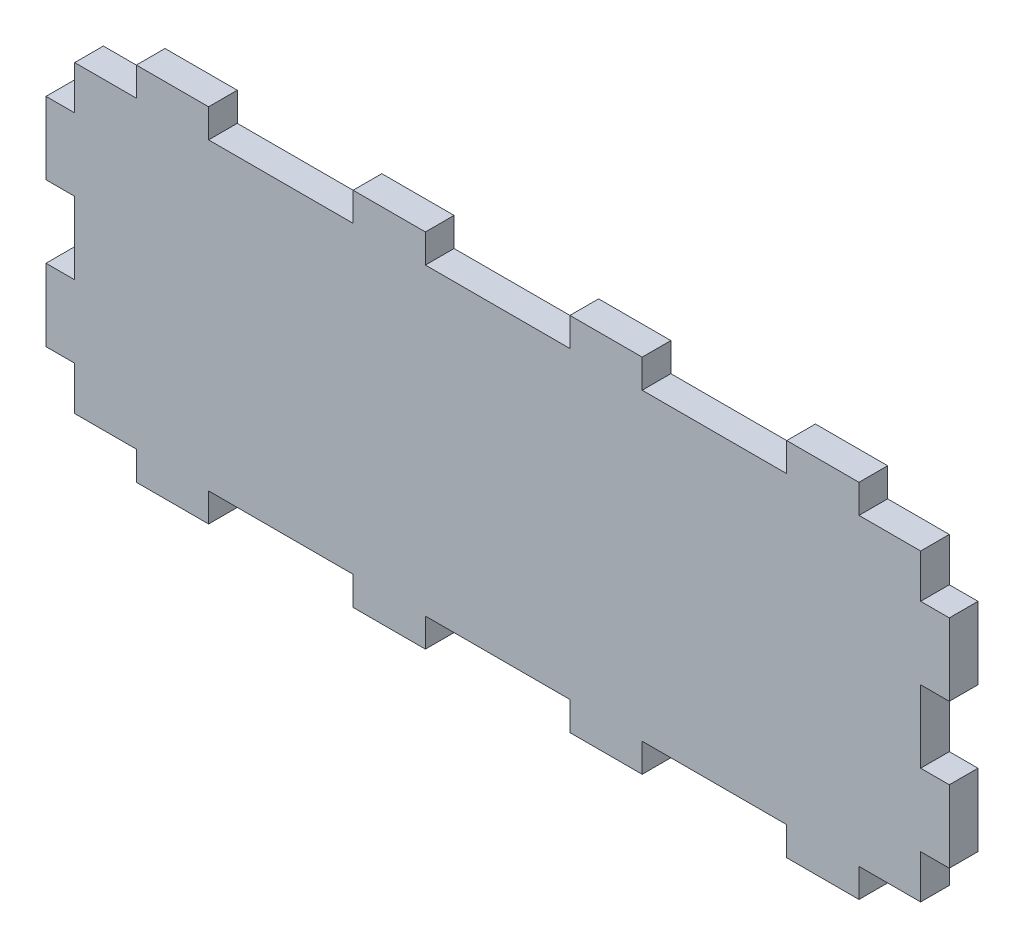
SolidWorks part; units mm, degrees
ref_plane "Front Plane" through (0, 0, 0) normal (0, 0, 1) x (1, 0, 0)
ref_plane "Top Plane" through (0, 0, 0) normal (0, 1, 0) x (1, 0, 0)
ref_plane "Right Plane" through (0, 0, 0) normal (1, 0, 0) x (0, 0, -1)
sketch "Sketch1" plane through (0, 0, 0) normal (0, 0, 1) x (1, 0, 0)
  line L1 (0, 0) -> (100, 0)
  line L2 (0, 0) -> (0, -40)
  line L3 (0, -40) -> (100, -40)
  line L4 (100, 0) -> (100, -40)
  dimension "D1" = 40
  dimension "D2" = 100
extrude "Boss-Extrude1" add sketch "Sketch1" along normal blind 3.175
sketch "Sketch2" plane through (0, 0, 3.175) normal (0, 0, 1) x (1, 0, 0)
  line L0 (0, -20) -> (100, -20) construction
  line L1 (0, 0) -> (0, -40) construction
  line L2 (100, -40) -> (100, 0) construction
  line L3 (50, 0) -> (50, -40) construction
  line L4 (100, 0) -> (0, 0) construction
  line L5 (0, -40) -> (100, -40) construction
  line L6 (10, -40) -> (10, -36.825)
  line L7 (10, -3.175) -> (0, -3.175)
  line L11 (42, -40) -> (58, -40)
  line L13 (42, -36.825) -> (58, -36.825)
  line L14 (58, -40) -> (58, -36.825)
  line L15 (66, -40) -> (82, -40)
  line L16 (66, -40) -> (66, -36.825)
  line L17 (66, -36.825) -> (82, -36.825)
  line L18 (82, -40) -> (82, -36.825)
  line L19 (100, -40) -> (90, -40)
  line L20 (100, -40) -> (100, -36.825)
  line L21 (100, -36.825) -> (90, -36.825)
  line L22 (90, -40) -> (90, -36.825)
  line L23 (0, -36.825) -> (10, -36.825)
  line L24 (0, -40) -> (0, -36.825)
  line L25 (0, -40) -> (10, -40)
  line L26 (18, -40) -> (18, -36.825)
  line L27 (34, -36.825) -> (18, -36.825)
  line L28 (34, -40) -> (34, -36.825)
  line L29 (34, -40) -> (18, -40)
  line L30 (42, -40) -> (42, -36.825)
  line L31 (34, 0) -> (18, 0)
  line L32 (0, 0) -> (10, 0)
  line L33 (100, -3.175) -> (90, -3.175)
  line L34 (42, 0) -> (42, -3.175)
  line L35 (34, 0) -> (34, -3.175)
  line L36 (34, -3.175) -> (18, -3.175)
  line L37 (18, 0) -> (18, -3.175)
  line L38 (0, 0) -> (0, -3.175)
  line L40 (90, 0) -> (90, -3.175)
  line L41 (100, 0) -> (100, -3.175)
  line L42 (100, 0) -> (90, 0)
  line L43 (82, 0) -> (82, -3.175)
  line L44 (66, -3.175) -> (82, -3.175)
  line L45 (66, 0) -> (66, -3.175)
  line L46 (66, 0) -> (82, 0)
  line L47 (58, 0) -> (58, -3.175)
  line L48 (42, -3.175) -> (58, -3.175)
  line L50 (42, 0) -> (58, 0)
  line L51 (10, 0) -> (10, -3.175)
  dimension "D4" = 3.175
  dimension "D5" = 16
  dimension "D6" = 3.175
  dimension "D7" = 8
  dimension "D8" = 3.175
  dimension "D9" = 8
extrude "Cut-Extrude1" cut sketch "Sketch2" against normal up to next
sketch "Sketch3" plane through (0, 0, 3.175) normal (0, 0, 1) x (1, 0, 0)
  line L0 (0, -20) -> (100, -20) construction
  line L1 (0, -3.175) -> (0, -36.825) construction
  line L2 (100, -36.825) -> (100, -3.175) construction
  line L3 (50, -3.175) -> (50, -36.825) construction
  line L4 (42, -3.175) -> (58, -3.175) construction
  line L5 (58, -36.825) -> (42, -36.825) construction
  line L6 (3.175, -36.825) -> (3.175, -32)
  line L7 (0, -32) -> (3.175, -32)
  line L8 (0, -24) -> (0, -16)
  line L9 (0, -16) -> (3.175, -16)
  line L10 (3.175, -24) -> (3.175, -16)
  line L11 (0, -3.175) -> (3.175, -3.175)
  line L12 (0, -3.175) -> (0, -8)
  line L13 (0, -8) -> (3.175, -8)
  line L14 (3.175, -3.175) -> (3.175, -8)
  line L15 (0, -36.825) -> (0, -32)
  line L16 (0, -36.825) -> (3.175, -36.825)
  line L17 (0, -24) -> (3.175, -24)
  line L18 (100, -24) -> (96.825, -24)
  line L19 (100, -36.825) -> (96.825, -36.825)
  line L20 (100, -36.825) -> (100, -32)
  line L21 (96.825, -3.175) -> (96.825, -8)
  line L22 (100, -8) -> (96.825, -8)
  line L23 (100, -3.175) -> (100, -8)
  line L24 (100, -3.175) -> (96.825, -3.175)
  line L25 (96.825, -24) -> (96.825, -16)
  line L26 (100, -16) -> (96.825, -16)
  line L27 (100, -24) -> (100, -16)
  line L28 (100, -32) -> (96.825, -32)
  line L29 (96.825, -36.825) -> (96.825, -32)
  point P24 (3.175, -20)
  point P37 (96.825, -20)
  dimension "D1" = 3.175
  dimension "D2" = 3.175
  dimension "D3" = 4
  dimension "D4" = 8
extrude "Cut-Extrude2" cut sketch "Sketch3" against normal up to next
